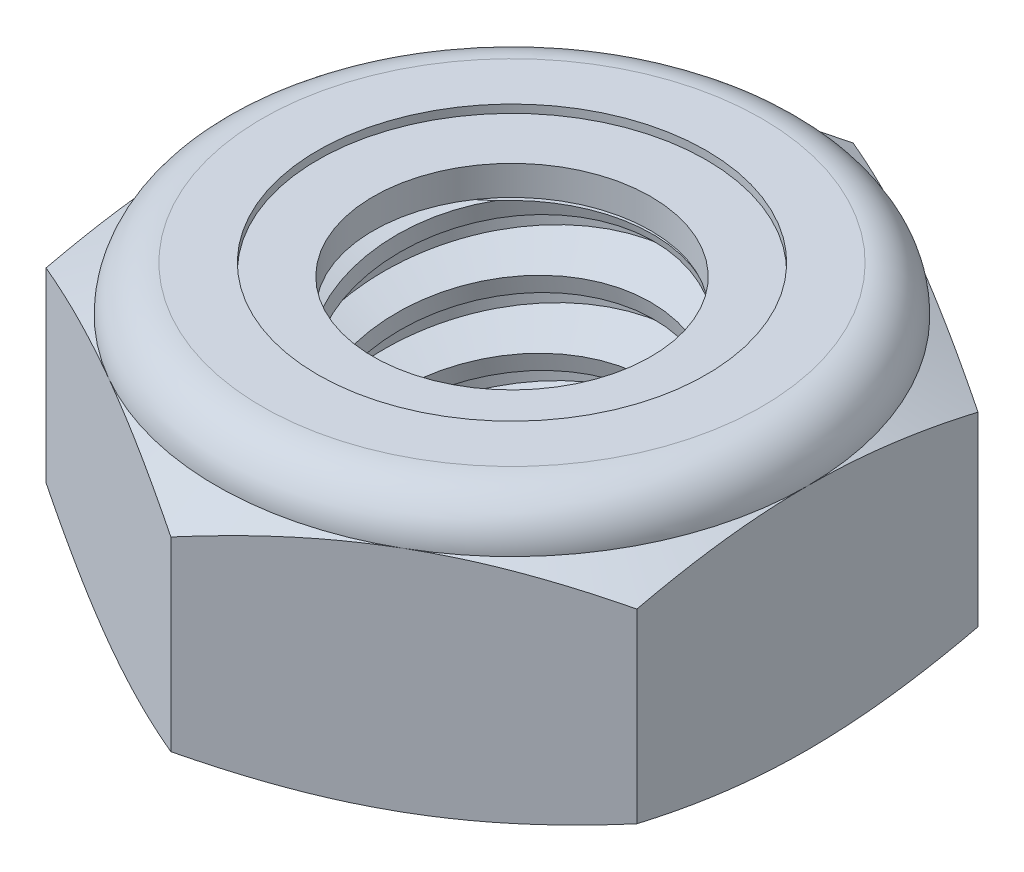
SolidWorks part; units mm, degrees
ref_plane "Front" through (0, 0, 0) normal (0, 0, 1) x (1, 0, 0)
ref_plane "Top" through (0, 0, 0) normal (0, 1, 0) x (1, 0, 0)
ref_plane "Right" through (0, 0, 0) normal (1, 0, 0) x (0, 0, -1)
sketch "Sketch1" plane through (0, 0, 0) normal (0, 1, 0) x (1, 0, 0)
  line L1 (0, 6.4158) -> (-5.5563, 3.2079)
  line L2 (-5.5563, 3.2079) -> (-5.5562, -3.2079)
  line L3 (-5.5562, -3.2079) -> (0, -6.4158)
  line L4 (0, -6.4158) -> (5.5562, -3.2079)
  line L5 (5.5562, -3.2079) -> (5.5562, 3.2079)
  line L6 (5.5562, 3.2079) -> (0, 6.4158)
  circle A0 centre (0, 0) radius 5.5562 construction
  dimension "Hex Flats" = 11.1125
extrude "Extrude1" add sketch "Sketch1" along normal blind 5.1594
sketch "Sketch2" plane through (0, 0, 0) normal (1, 0, 0) x (0, 0, -1)
  line L0 (-3.175, 0) -> (-3.175, 5.1594) construction
  line L1 (0, 0) -> (3.175, 0)
  line L2 (0, 0) -> (0, 5.1594)
  line L3 (0, 5.1594) -> (3.175, 5.1594)
  line L4 (3.175, 0) -> (3.175, 5.1594)
  line L5 (-3.2079, 5.1594) -> (3.2079, 5.1594) construction
  line L7 (0, -3.175) -> (0, 0) construction
  dimension "Thread Dia" = 6.35
revolve "Revolve1" add sketch "Sketch2" angle 360 about L7
sketch "Sketch3" plane through (0, 0, 0) normal (1, 0, 0) x (0, 0, -1)
  line L0 (3.175, 5.1594) -> (-3.175, 5.1594) construction
  line L1 (-3.175, 5.1594) -> (-3.175, 3.8894) construction
  line L2 (-3.175, 3.8894) -> (3.175, 5.1594) construction
  line L3 (3.175, 5.1594) -> (3.2061, 5.0037) construction
  line L4 (3.2061, 5.0037) -> (3.4241, 3.914)
  line L5 (3.4241, 3.914) -> (2.6722, 4.1684)
  line L6 (2.6722, 4.1684) -> (2.6099, 4.4797)
  line L7 (2.6099, 4.4797) -> (3.2061, 5.0037)
  line L8 (2.641, 4.3241) -> (3.3151, 4.4589) construction
  line L9 (3.175, 5.1594) -> (3.175, 4.4309) construction
  line L10 (3.175, 4.4309) -> (-3.175, 3.1609) construction
  line L11 (-3.175, 3.1609) -> (-3.175, 3.8894) construction
  line L12 (-0.2727, 5.1594) -> (0.2727, 2.4323) construction
  line L13 (-3.175, 0) -> (-3.175, 5.1594) construction
  line L14 (0, 5.1594) -> (3.175, 5.1594) construction
  line L15 (3.175, 0) -> (3.175, 5.1594) construction
  point P13 (0, 3.7959)
  dimension "D1" = 0.1588
  dimension "D2" = 0.3175
  dimension "Thread Pitch" = 1.27
  dimension "D4" = 60
  dimension "D5" = 1.27
revolve "Cut-Revolve1" cut sketch "Sketch3" angle 360 about L12
pattern_linear "LPattern1" count 4 spacing 1.27 along (0, -1, 0) count 2 spacing 1.27 along (0, 1, 0) of "Cut-Revolve1"
sketch "Sketch4" plane through (0, 0, 0) normal (1, 0, 0) x (0, 0, -1)
  line L0 (0, 5.1594) -> (3.175, 5.1594)
  line L1 (3.175, 5.1594) -> (2.6099, 4.8959)
  line L2 (2.6099, 4.8959) -> (2.6099, 0.2635)
  line L3 (2.6099, 0.2635) -> (3.175, 0)
  line L4 (3.175, 0) -> (0, 0)
  line L5 (0, 0) -> (0, 5.1594)
  line L6 (3.175, 0) -> (3.175, 5.1594) construction
  line L7 (0, 5.1594) -> (3.175, 5.1594) construction
  line L8 (0, 0) -> (3.175, 0) construction
  line L9 (0, 0) -> (0, 5.1594) construction
  line L10 (0, 5.1594) -> (0, 5.7829) construction
  dimension "D1" = 25
revolve "Cut-Revolve2" cut sketch "Sketch4" angle 360 about L10
combine bodies "Combine1" operation type subtract main body 112 bodies to subtract 111
sketch "Sketch5" plane through (0, 0, 0) normal (1, 0, 0) x (0, 0, -1)
  line L0 (0, 0) -> (5.5562, 0)
  line L1 (5.5562, 0) -> (6.4158, 0.4008)
  line L2 (6.4158, 0.4008) -> (6.4158, 3.8987)
  line L3 (6.4158, 3.8987) -> (5.5562, 4.2995)
  line L4 (4.6964, 5.1594) -> (4.6964, 6.4294)
  line L5 (4.6964, 6.4294) -> (7.6858, 6.4294)
  line L6 (7.6858, 6.4294) -> (7.6858, -1.27)
  line L7 (7.6858, -1.27) -> (0, -1.27)
  line L8 (0, -1.27) -> (0, 0)
  line L9 (5.5562, 4.2995) -> (5.5562, 0) construction
  line L10 (0, 0) -> (3.175, 0) construction
  line L13 (6.4158, 2.1497) -> (7.6858, 2.1497) construction
  line L14 (6.4158, 5.1594) -> (6.4158, 0) construction
  line L15 (0, 0) -> (0, 6.4294) construction
  line L20 (0, 6.4294) -> (4.6964, 6.4294) construction
  line L22 (0, 5.1594) -> (3.175, 5.1594) construction
  arc A0 (5.5562, 4.2995) -> (4.6964, 5.1594) centre (4.6964, 4.2995) ccw
  dimension "D1" = 25
  dimension "D2" = 1.27
  dimension "D3" = 5.1594
  dimension "D4" = 0.8599
revolve "Cut-Revolve3" cut sketch "Sketch5" angle 360 about L15
sketch "Sketch6" plane through (0, 0, 0) normal (1, 0, 0) x (0, 0, -1)
  line L0 (0, 4.2995) -> (5.4038, 4.2995)
  line L1 (4.6964, 5.007) -> (3.6531, 5.007)
  line L2 (0, 6.4294) -> (0, 4.2995)
  line L3 (3.6531, 6.4294) -> (0, 6.4294)
  line L4 (0, 6.4294) -> (4.6964, 6.4294) construction
  line L5 (0, 0) -> (0, 6.4294) construction
  line L6 (0, 6.4294) -> (0, 44.323) construction
  line L7 (3.6531, 5.007) -> (3.6531, 6.4294)
  line L8 (4.6964, 5.1594) -> (4.6964, 5.007) construction
  line L9 (3.6531, 5.007) -> (2.6099, 5.007) construction
  line L10 (2.6099, 5.007) -> (2.6099, 4.8959) construction
  arc A0 (5.4038, 4.2995) -> (4.6964, 5.007) centre (4.6964, 4.2995) ccw
  arc A1 (5.5562, 4.2995) -> (4.6964, 5.1594) centre (4.6964, 4.2995) ccw construction
  dimension "D1" = 0.1524
revolve "Cut-Revolve4" cut sketch "Sketch6" angle 360 about L6
sketch "Sketch7" plane through (0, 0, 0) normal (1, 0, 0) x (0, 0, -1)
  line L0 (2.6099, 4.3757) -> (5.323, 4.3757)
  line L1 (4.6964, 4.9308) -> (2.6099, 4.9308)
  line L2 (2.6099, 4.9308) -> (2.6099, 4.3757)
  line L3 (2.6099, 4.3757) -> (0, 4.3757) construction
  line L4 (0, 4.3757) -> (0, 4.9308) construction
  line L5 (0, 4.9308) -> (2.6099, 4.9308) construction
  line L6 (2.6099, 4.3757) -> (2.6099, 4.2995) construction
  line L7 (0, 4.2995) -> (5.4038, 4.2995) construction
  line L8 (4.6964, 4.9308) -> (4.6964, 5.007) construction
  arc A0 (5.323, 4.3757) -> (4.6964, 4.9308) centre (4.6964, 4.2995) ccw
  arc A2 (5.4038, 4.2995) -> (4.6964, 5.007) centre (4.6964, 4.2995) ccw construction
  dimension "D1" = 0.0762
revolve "Revolve2" add sketch "Sketch7" angle 360 about L4
equation "\"D1@Sketch3\"=\"Thread Pitch@Sketch3\"/8"
equation "\"D2@Sketch3\"=\"Thread Pitch@Sketch3\"/4"
equation "\"D5@Sketch3\"=\"Thread Pitch@Sketch3\""
equation "\"D4@LPattern1\"=\"Thread Pitch@Sketch3\""
equation "\"D3@LPattern1\"=\"Thread Pitch@Sketch3\""
equation "\"D1@LPattern1\"=\"Height@Extrude1\"/\"Thread Pitch@Sketch3\""
equation "\"D4@Sketch5\"=\"Height@Extrude1\"/6"
